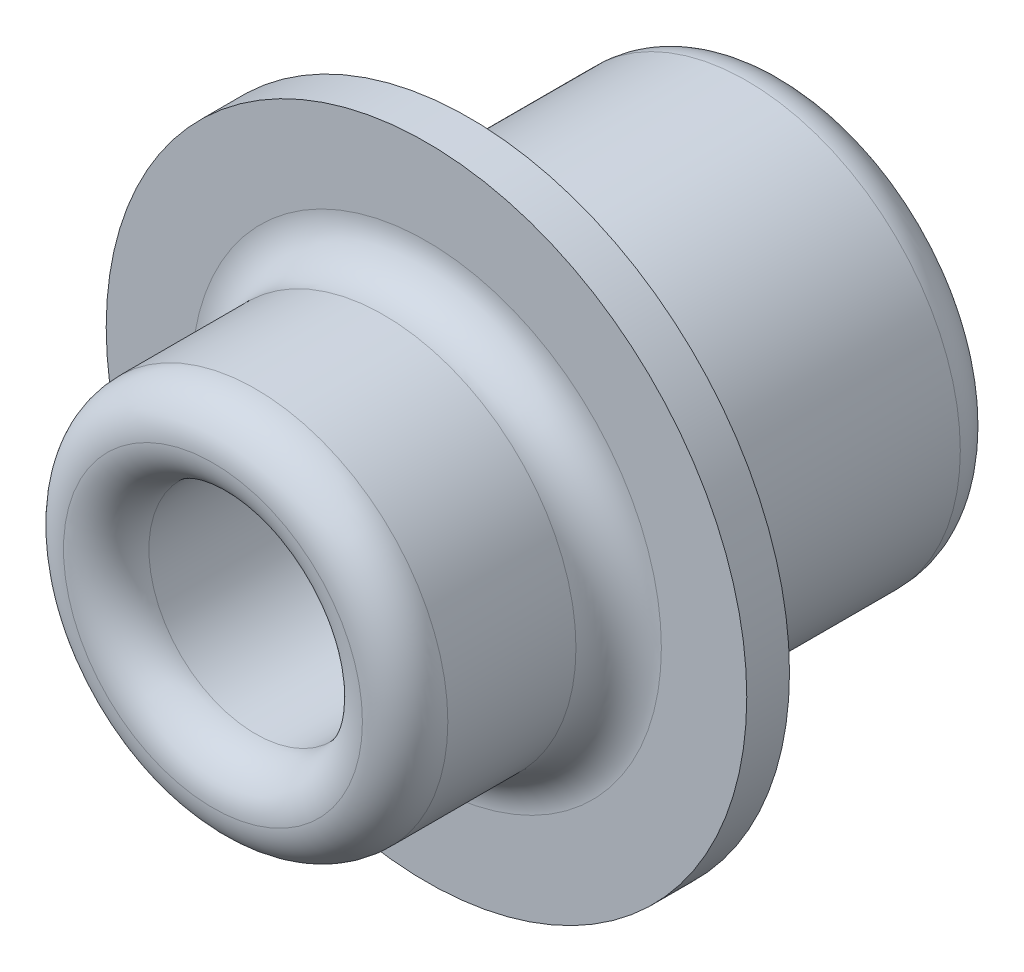
SolidWorks part; units mm, degrees
ref_plane "前视基准面" through (0, 0, 0) normal (0, 0, 1) x (1, 0, 0)
ref_plane "上视基准面" through (0, 0, 0) normal (0, 1, 0) x (1, 0, 0)
ref_plane "右视基准面" through (0, 0, 0) normal (1, 0, 0) x (0, 0, -1)
other "Configuration Table"
sketch "草图1" plane through (0, 0, 0) normal (0, 0, 1) x (1, 0, 0)
  circle A0 centre (0, 0) radius 10
  circle A1 centre (0, 0) radius 5.1
  dimension "D1" = 20
  dimension "D2" = 10.2
extrude "凸台-拉伸1" add sketch "草图1" along normal blind 15
sketch "草图2" plane through (0, 0, 15) normal (0, 0, 1) x (1, 0, 0)
  circle A0 centre (0, 0) radius 5
  circle A1 centre (0, 0) radius 15
  dimension "D1" = 30
  dimension "D2" = 10
extrude "凸台-拉伸2" add sketch "草图2" along normal blind 2
sketch "草图3" plane through (0, 0, 17) normal (0, 0, 1) x (1, 0, 0)
  circle A0 centre (0, 0) radius 9
  circle A1 centre (0, 0) radius 5 construction
  circle A2 centre (0, 0) radius 5
  dimension "D1" = 18
extrude "凸台-拉伸3" add sketch "草图3" along normal blind 10
fillet "圆角1" radius 2 4 edges at (5, 0, 27) (9, 0, 27) (10, 0, 0) (9, 0, 17)
